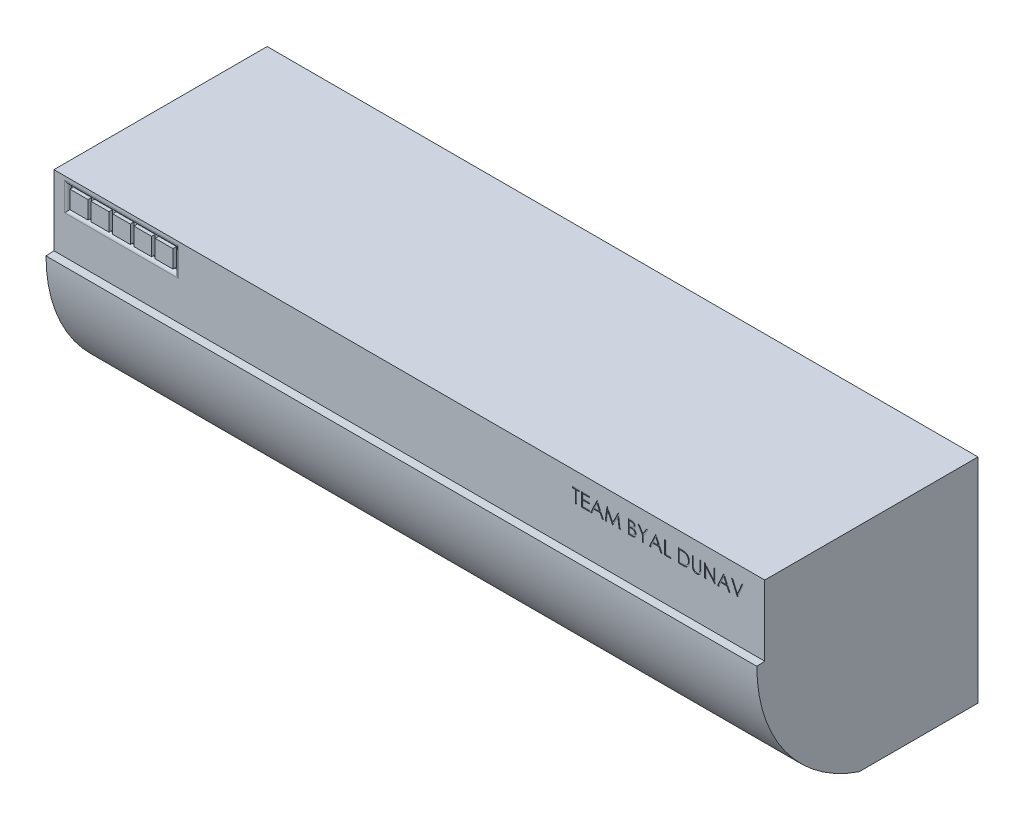
SolidWorks part; units mm, degrees
ref_plane "Front Plane" through (0, 0, 0) normal (0, 0, 1) x (1, 0, 0)
ref_plane "Top Plane" through (0, 0, 0) normal (0, 1, 0) x (1, 0, 0)
ref_plane "Right Plane" through (0, 0, 0) normal (1, 0, 0) x (0, 0, -1)
sketch "Sketch1" plane through (0, 0, 0) normal (1, 0, 0) x (0, 0, -1)
  line L1 (150.0008, -150.0008) -> (50.4794, -150.0008)
  line L2 (150.0008, -150.0008) -> (150.0008, 149.9992)
  line L3 (150.0008, 149.9992) -> (-149.9992, 149.9992)
  line L4 (-149.9992, 51.1376) -> (-149.9992, 149.9992)
  line L5 (150.0008, -150.0008) -> (-149.9992, 149.9992) construction
  line L6 (150.0008, 149.9992) -> (-91.2819, -91.2809) construction
  arc A0 (-149.9992, 51.1376) -> (50.4794, -150.0008) centre (50.4794, 50.4788) ccw
  point P0 (0, 0)
  dimension "D1" = 300
extrude "Boss-Extrude1" add sketch "Sketch1" along normal blind 1000
sketch "Sketch5" plane through (1000, 0, 0) normal (1, 0, 0) x (0, 0, -1)
  line L0 (-161.1305, 50.4788) -> (-149.9992, 51.1376)
  line L1 (50.4794, -150.0008) -> (50.4794, -161.131)
  line L6 (-149.9992, 149.9992) -> (-149.9992, 51.1376)
  line L7 (50.4794, -150.0008) -> (150.0008, -150.0008)
  line L8 (150.0008, -150.0008) -> (150.0008, 149.9992)
  line L9 (150.0008, 149.9992) -> (-149.9992, 149.9992)
  arc A0 (-161.1305, 50.4788) -> (50.4794, -161.131) centre (50.4794, 50.4788) ccw
  arc A2 (-149.9992, 51.1376) -> (50.4794, -150.0008) centre (50.4794, 50.4788) ccw
  arc A3 (-149.9992, 51.1376) -> (50.4794, -150.0008) centre (50.4794, 50.4788) ccw
  dimension "D1" = 0
extrude "Boss-Extrude3" add sketch "Sketch5" against normal blind 1000
sketch "Sketch6" plane through (1000, 0, 0) normal (1, 0, 0) x (0, 0, -1)
  line L1 (150.0008, -150.0008) -> (-134.3629, -150.0008)
  line L2 (150.0008, -150.0008) -> (150.0008, -166.6705)
  line L3 (150.0008, -166.6705) -> (-134.3629, -166.6705)
  line L4 (-134.3629, -150.0008) -> (-134.3629, -166.6705)
  line L5 (150.0008, -150.0008) -> (-134.3629, -166.6705) construction
  line L6 (150.0008, -166.6705) -> (-134.3629, -150.0008) construction
  point P4 (7.8189, -158.3357)
extrude "Cut-Extrude2" cut sketch "Sketch6" against normal blind 1000
sketch "Sketch7" plane through (0, 0, 149.9992) normal (0, 0, 1) x (1, 0, 0)
  line L0 (0, 149.9992) -> (0, 51.1376) construction
  line L1 (20, 139.9992) -> (170, 139.9992)
  line L2 (20, 139.9992) -> (20, 109.9992)
  line L3 (20, 109.9992) -> (170, 109.9992)
  line L4 (170, 139.9992) -> (170, 109.9992)
  line L5 (47.9743, 137.0706) -> (47.9743, 137.4992)
  line L7 (1000, 149.9992) -> (0, 149.9992) construction
  line L9 (112.5, 137.4992) -> (137.5, 137.4992)
  line L15 (52.5, 139.9992) -> (47.0257, 139.9992)
  line L17 (47.9743, 137.4992) -> (47.9167, 137.4992)
  line L18 (107.5, 112.4992) -> (82.5, 112.4992)
  line L19 (20, 109.9992) -> (22.5, 109.9992)
  line L21 (20, 139.9992) -> (22.5, 139.9992)
  line L23 (17.9144, 112.4858) -> (17.9167, 112.4992) construction
  line L24 (17.9144, 137.5126) -> (17.9167, 137.4992) construction
  line L25 (82.5, 109.9992) -> (77.5, 109.9992)
  line L27 (82.5, 139.9992) -> (77.5, 139.9992)
  line L29 (52.0257, 112.4992) -> (52.0257, 137.4992)
  line L30 (142.5, 137.4992) -> (167.5, 137.4992)
  line L31 (112.5, 109.9992) -> (107.5, 109.9992)
  line L33 (112.5, 139.9992) -> (107.5, 139.9992)
  line L36 (167.5, 112.4992) -> (167.5, 137.4992)
  line L37 (142.5, 109.9992) -> (137.5, 109.9992)
  line L38 (142.5, 112.4992) -> (142.5, 137.4992)
  line L39 (142.5, 139.9992) -> (137.5, 139.9992)
  line L40 (137.5, 112.4992) -> (137.5, 137.4992)
  line L43 (170, 109.9992) -> (167.5, 109.9992)
  line L45 (170, 139.9992) -> (167.5, 139.9992)
  line L47 (107.5, 112.4992) -> (107.5, 137.4992)
  line L48 (172.0856, 137.5126) -> (172.0833, 137.4992) construction
  line L54 (112.5, 112.4992) -> (112.5, 137.4992)
  line L60 (170, 109.9992) -> (20, 109.9992)
  line L61 (22.5, 137.4992) -> (47.9167, 137.4992)
  line L62 (52.0257, 137.4992) -> (52.0833, 137.4992)
  line L67 (167.5, 112.4992) -> (142.5, 112.4992)
  line L68 (137.5, 112.4992) -> (112.5, 112.4992)
  line L70 (170, 109.9992) -> (170, 139.9992)
  line L71 (170, 139.9992) -> (20, 139.9992)
  line L72 (20, 109.9992) -> (20, 139.9992)
  line L73 (77.5, 112.4992) -> (52.0257, 112.4992)
  line L74 (47.9743, 112.4992) -> (22.5, 112.4992)
  line L79 (52.0833, 137.4992) -> (77.5, 137.4992)
  line L81 (77.5, 112.4992) -> (77.5, 137.4992)
  line L84 (22.5, 112.4992) -> (22.5, 137.4992)
  line L85 (80, 110.4831) -> (77.5, 110.5637) construction
  line L86 (82.0833, 137.4992) -> (107.5, 137.4992)
  line L88 (82.5, 112.4992) -> (82.5, 137.4992)
  line L94 (47.9743, 112.4992) -> (47.9743, 137.0706)
  point P4 (95, 124.9992)
  point P18 (50, 121.9992)
  point P23 (20, 124.9992)
  point P25 (95, 124.9992)
  point P28 (80, 124.9992)
  point P33 (110, 124.9992)
  point P38 (140, 124.9992)
  point P43 (170, 124.9992)
  point P48 (95, 139.9992)
  point P53 (95, 109.9992)
  dimension "D1" = 30
  dimension "D2" = 150
  dimension "D3" = 20
  dimension "D4" = 10
  dimension "D13" = 5
extrude "Cut-Extrude5" cut sketch "Sketch7" against normal blind 5 contours L4 L1 L2 L3 L94 L74 L84 L61 L17 L5 L81 L73 L29 L62 L79 L36 L67 L38 L30 L40 L68 L54 L9 L18 L88 L86 region at (21.25, 138.4695, 149.9992)
fillet "Fillet2" radius 5 4 edges at (95, 109.9992, 149.9992) (170, 124.9992, 149.9992) (20, 124.9992, 149.9992) (95, 139.9992, 149.9992)
sketch "Sketch8" plane through (0, 0, 149.9992) normal (0, 0, 1) x (1, 0, 0)
  line L1 (1000, 149.9992) -> (700, 149.9992) construction
  line L2 (1000, 149.9992) -> (1000, 109.9992) construction
  line L3 (1000, 109.9992) -> (700, 109.9992) construction
  line L4 (700, 149.9992) -> (700, 109.9992) construction
  line L5 (1000, 149.9992) -> (700, 109.9992) construction
  line L6 (1000, 109.9992) -> (700, 149.9992) construction
  text T0 "TEAM BYAL DUNAV" font "Century Gothic" height in points 72
  point P4 (850, 129.9992)
  dimension "D1" = 300
  dimension "D2" = 40
extrude "Cut-Extrude6" cut sketch "Sketch8" against normal blind 1
